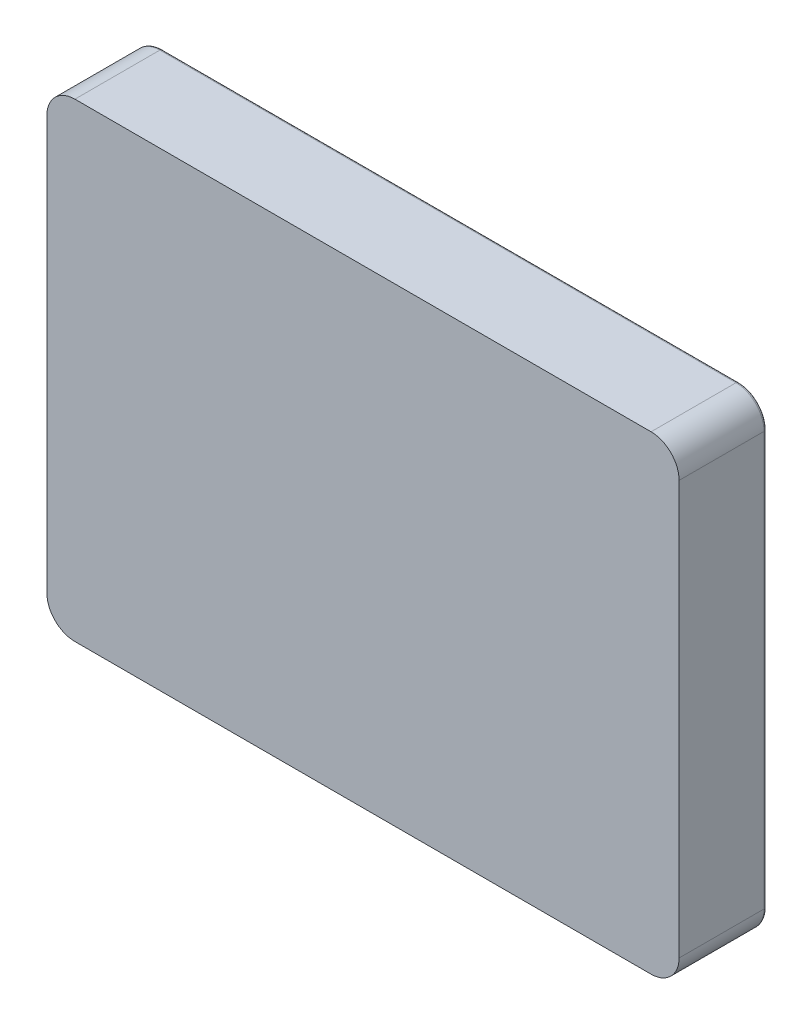
SolidWorks part; units mm, degrees
ref_plane "Plan de face" through (0, 0, 0) normal (0, 0, 1) x (1, 0, 0)
ref_plane "Plan de dessus" through (0, 0, 0) normal (0, 1, 0) x (1, 0, 0)
ref_plane "Plan de droite" through (0, 0, 0) normal (1, 0, 0) x (0, 0, -1)
sketch "Esquisse1" plane through (0, 0, 0) normal (0, 0, 1) x (1, 0, 0)
  line L1 (-102.649, -83.693) -> (102.649, -83.693)
  line L2 (-112.649, -73.693) -> (-112.649, 73.693)
  line L3 (-102.649, 83.693) -> (102.649, 83.693)
  line L4 (112.649, -73.693) -> (112.649, 73.693)
  line L5 (-112.649, -83.693) -> (112.649, 83.693) construction
  line L6 (-112.649, 83.693) -> (112.649, -83.693) construction
  line L7 (-102.9632, -76.4969) -> (102.9632, -76.4969)
  line L8 (-102.9632, -76.4969) -> (-102.9632, 76.4969)
  line L9 (-102.9632, 76.4969) -> (102.9632, 76.4969)
  line L10 (102.9632, -76.4969) -> (102.9632, 76.4969)
  line L11 (-102.9632, -76.4969) -> (102.9632, 76.4969) construction
  line L12 (-102.9632, 76.4969) -> (102.9632, -76.4969) construction
  arc A0 (-112.649, -73.693) -> (-102.649, -83.693) centre (-102.649, -73.693) ccw
  arc A1 (102.649, -83.693) -> (112.649, -73.693) centre (102.649, -73.693) ccw
  arc A2 (112.649, 73.693) -> (102.649, 83.693) centre (102.649, 73.693) ccw
  arc A3 (-112.649, 73.693) -> (-102.649, 83.693) centre (-102.649, 73.693) cw
  point P0 (0, 0)
  point P18 (0, 0)
  dimension "D3" = 10
  dimension "D1" = 225.298
  dimension "D2" = 167.386
  dimension "D4" = 256.54
extrude "Boss.-Extru.2" add sketch "Esquisse1" along normal blind 31.242 contours L3 A2 L4 A1 L1 A0 L2 A3
extrude "Enlèv. mat.-Extru.3" cut sketch "Esquisse1<6>" along normal blind 1 contours L10 L9 L8 L7
sketch "Esquisse1<6>" plane through (0, 0, 0) normal (0, 0, 1) x (1, 0, 0) same geometry as "Esquisse1"
fillet "Congé2" radius 1 8 edges at (-109.7201, 80.7641, 0) (-112.649, 0, 0) (-109.7201, -80.7641, 0) (0, -83.693, 0) (109.7201, -80.7641, 0) (112.649, 0, 0) (109.7201, 80.7641, 0) (0, 83.693, 0)
